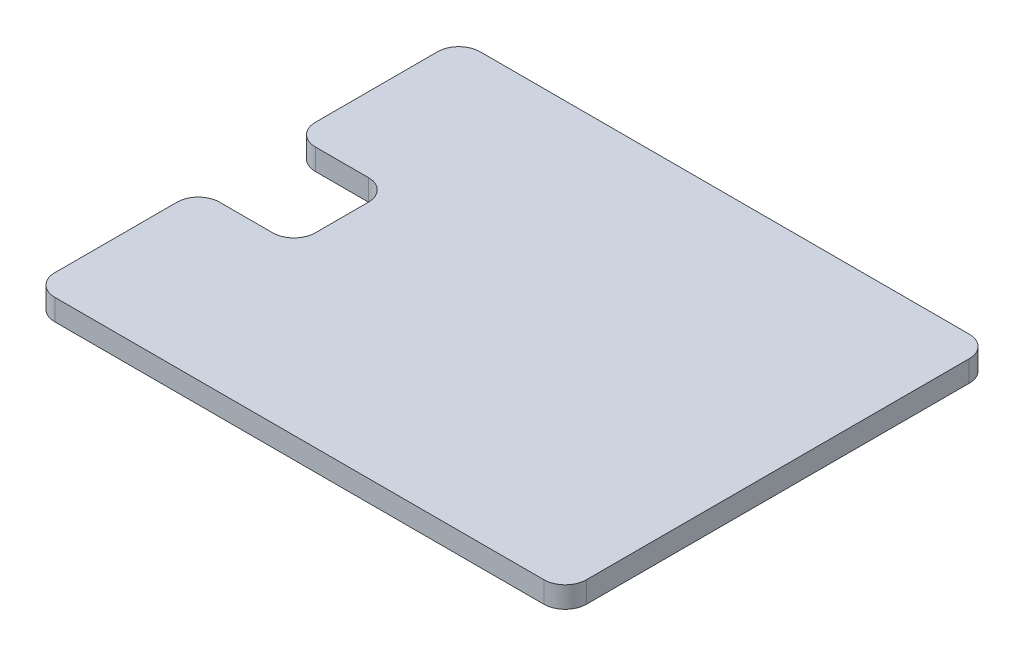
SolidWorks part; units mm, degrees
ref_plane "Front" through (0, 0, 0) normal (0, 0, 1) x (1, 0, 0)
ref_plane "Top" through (0, 0, 0) normal (0, 1, 0) x (1, 0, 0)
ref_plane "Right" through (0, 0, 0) normal (1, 0, 0) x (0, 0, -1)
sketch "Эскиз3" plane through (0, 0, 0) normal (0, 0, 1) x (1, 0, 0)
  line L0 (0, 0) -> (-10.3815, 0) construction
  line L1 (-22.5, 5) -> (-17.5, 5)
  line L2 (-22.5, 5) -> (-20.5, 13)
  line L3 (-17.5, 5) -> (-15.5, 13)
  line L4 (-20.5, 13) -> (-15.5, 13)
  line L6 (-21.625, 7.8146) -> (-23.25, 5)
  line L7 (-23.25, 5) -> (-21.625, 2.1854)
  line L8 (-21.625, 2.1854) -> (-18.375, 2.1854)
  line L9 (-18.375, 2.1854) -> (-16.75, 5)
  line L10 (-16.75, 5) -> (-18.375, 7.8146)
  line L11 (-18.375, 7.8146) -> (-21.625, 7.8146)
  circle A0 centre (-20, 5) radius 5
  circle A1 centre (-20, 5) radius 2.8146 construction
  circle A2 centre (-20, 5) radius 1.6
  point P6 (-20, 5)
  dimension "D1" = 10
  dimension "D6" = 8
  dimension "D7" = 3.2
  dimension "D2" = 20
  dimension "D3" = 5
  dimension "D4" = 2
  dimension "D5" = 6.5
extrude "Бобышка-Вытянуть3" add sketch "Эскиз3" along normal blind 8 contours A0 L3 L4 L2 | A0 region at (-18.2774, 11.3045, 0)
sketch "Эскиз4" plane through (0, 13, 0) normal (0, 1, 0) x (1, 0, 0)
  line L0 (-20.5, -8) -> (-15.5, -8) construction
  line L1 (20.5, 12) -> (-29.5, 12)
  line L2 (20.5, 12) -> (20.5, -28)
  line L3 (20.5, -28) -> (-29.5, -28)
  line L4 (-29.5, 12) -> (-29.5, -28)
  line L5 (-4.5, -28) -> (-4.5, 12) construction
  line L6 (20.5, -8) -> (-29.5, -8) construction
  point P0 (-4.5, 8)
  point P6 (-4.5, -8)
  dimension "D1" = 16
  dimension "D2" = 50
  dimension "D3" = 40
extrude "Бобышка-Вытянуть4" add sketch "Эскиз4" along normal blind 2
fillet "Скругление1" radius 2 4 edges at (20.5, 14, -12) (20.5, 14, 28) (-29.5, 14, -12) (-29.5, 14, 28)
extrude "Вырез-Вытянуть1" cut sketch "Эскиз3<3>" along normal blind 3 contours L6 L7 L8 L9 L10 L11
sketch "Эскиз3<3>" plane through (0, 0, 0) normal (0, 0, 1) x (1, 0, 0) same geometry as "Эскиз3"
extrude "Вырез-Вытянуть2" cut sketch "Эскиз3<4>" against normal through all both and the other way through all contours A2
sketch "Эскиз3<4>" plane through (0, 0, 0) normal (0, 0, 1) x (1, 0, 0) same geometry as "Эскиз3"
sketch "Эскиз6" plane through (0, 15, 0) normal (0, 1, 0) x (1, 0, 0)
  line L0 (-29.5, 10) -> (-29.5, -26) construction
  line L1 (-20.5, -3.5) -> (-29.5, -3.5)
  line L2 (-20.5, -3.5) -> (-20.5, -12.5)
  line L3 (-20.5, -12.5) -> (-29.5, -12.5)
  line L4 (-29.5, -3.5) -> (-29.5, -12.5)
  line L5 (-25, -12.5) -> (-25, -3.5) construction
  line L6 (-20.5, -8) -> (-29.5, -8) construction
  point P0 (-25, -8)
  dimension "D1" = 9
  dimension "D2" = 9
extrude "Вырез-Вытянуть3" cut sketch "Эскиз6" against normal blind 2
fillet "Скругление3" radius 2 4 edges at (-29.5, 14, 12.5) (-29.5, 14, 3.5) (-20.5, 14, 3.5) (-20.5, 14, 12.5)
extrude "Бобышка-Вытянуть5" add sketch "Эскиз3<5>" along normal blind 16 contours A0 L3 L4 L2 region at (-18.2774, 11.3045, 0)
sketch "Эскиз3<5>" plane through (0, 0, 0) normal (0, 0, 1) x (1, 0, 0) same geometry as "Эскиз3"
